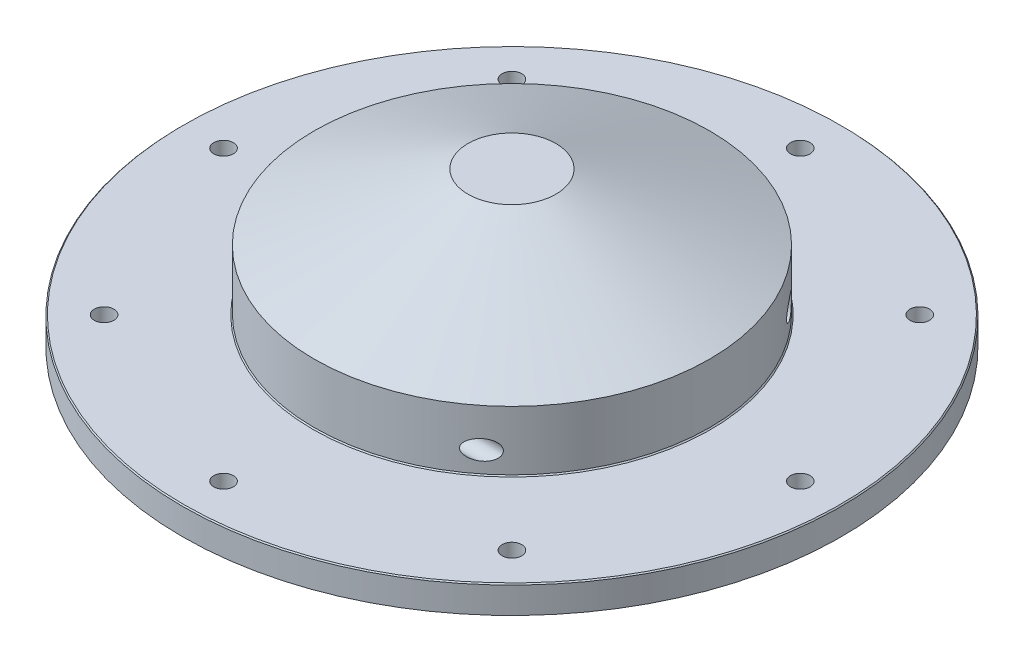
SolidWorks part; units mm, degrees
ref_plane "Front Plane" through (0, 0, 0) normal (0, 0, 1) x (1, 0, 0)
ref_plane "Top Plane" through (0, 0, 0) normal (0, 1, 0) x (1, 0, 0)
ref_plane "Right Plane" through (0, 0, 0) normal (1, 0, 0) x (0, 0, -1)
sketch "Sketch2" plane through (0, 0, 0) normal (0, 1, 0) x (1, 0, 0)
  circle A0 centre (0, 0) radius 38.1
  dimension "D1" = 76.2
extrude "Boss-Extrude1" add sketch "Sketch2" along normal blind 3.175
hole_wizard "Tap Drill for #4-40 Tap1" positions "Sketch3" profile "Sketch4" hole size "#4-40" standard "ANSI Inch" end condition through all
sketch "Sketch3" plane through (0, 0, 0) normal (0, -1, 0) x (-1, 0, 0)
  point P0 (0, -33.3375)
  dimension "D1" = 33.3375
sketch "Sketch4" plane through (0, 0, 33.3375) normal (1, 0, 0) x (0, 0, -1)
  line L0 (0, 0) -> (0, 3.175)
  line L1 (0, 3.175) -> (1.1303, 3.175)
  line L2 (1.1303, 3.175) -> (1.1303, 0)
  line L5 (1.1303, 0) -> (0, 0)
  line L11 (0, -6.35) -> (0, 107.95) construction
  dimension "Thru Hole Dia." = 2.2606
  dimension "Thru Hole Depth" = 3.175
pattern_circular "CirPattern1" count 8 over 360 about axis through (0, 0, 0) along (0, 1, 0) of "Tap Drill for #4-40 Tap1"
sketch "Sketch5" plane through (0, 3.175, 0) normal (0, 1, 0) x (1, 0, 0)
  circle A0 centre (0, 0) radius 28.575
  dimension "D1" = 57.15
sketch "Sketch7" plane through (0, 3.175, 0) normal (0, 1, 0) x (1, 0, 0)
  circle A0 centre (0, 0) radius 22.86
  dimension "D1" = 45.72
extrude "Boss-Extrude2" add sketch "Sketch7" along normal blind 6.985
sketch "Sketch8" plane through (0, 0, 0) normal (0, -1, 0) x (1, 0, 0)
  circle A0 centre (0, 0) radius 19.05
  dimension "D1" = 38.1
extrude "Cut-Extrude1" cut sketch "Sketch8" against normal blind 8.255
hole_wizard "Tap Drill for #4-40 Tap2" positions "Sketch11" profile "Sketch12" hole size "#4-40" standard "ANSI Inch" end condition through all
sketch "Sketch11" plane through (0, 0, 0) normal (0, 0, 1) x (1, 0, 0)
  line L0 (0, -1.7463) -> (0, 1.7463) construction
  line L1 (22.86, 3.175) -> (-22.86, 3.175) construction
  point P0 (-17.78, 5.715)
  dimension "D1" = 17.78
  dimension "D2" = 2.54
sketch "Sketch12" plane through (-17.78, 5.715, 0) normal (1, 0, 0) x (0, 1, 0)
  line L0 (0, 0) -> (0, 38.1)
  line L1 (0, 38.1) -> (1.1303, 38.1)
  line L2 (1.1303, 38.1) -> (1.1303, 0)
  line L5 (1.1303, 0) -> (0, 0)
  line L11 (0, -6.35) -> (0, 107.95) construction
  dimension "Thru Hole Dia." = 2.2606
  dimension "Thru Hole Depth" = 38.1
pattern_circular "CirPattern2" count 4 over 360 about axis through (0, 10.16, 0) along (0, 1, 0) of "Tap Drill for #4-40 Tap2"
sketch "Sketch13" plane through (0, 10.16, 0) normal (0, 1, 0) x (1, 0, 0)
  circle A0 centre (0, 0) radius 22.86
  circle A1 centre (0, 0) radius 22.86 construction
  dimension "D1" = 0
ref_plane "Plane2" through (0, 17.78, 0) normal (0, 1, 0) x (1, 0, 0)
sketch "Sketch14" plane through (0, 17.78, 0) normal (0, 1, 0) x (1, 0, 0)
  circle A0 centre (0, 0) radius 5.08
  dimension "D1" = 10.16
loft "Loft2" add profiles "Sketch14", "Sketch13" connector at (-0.0647, 17.78, 5.0796) connector at (0, 10.16, 22.86)
fillet "Fillet1" radius 0.635 1 edges at (0, 8.255, -19.05)
chamfer "Chamfer1" distance 0.127 angle 45 1 edges at (0, 3.175, 38.1)
chamfer "Chamfer2" distance 0.127 angle 45 1 edges at (0, 3.175, 22.86)
